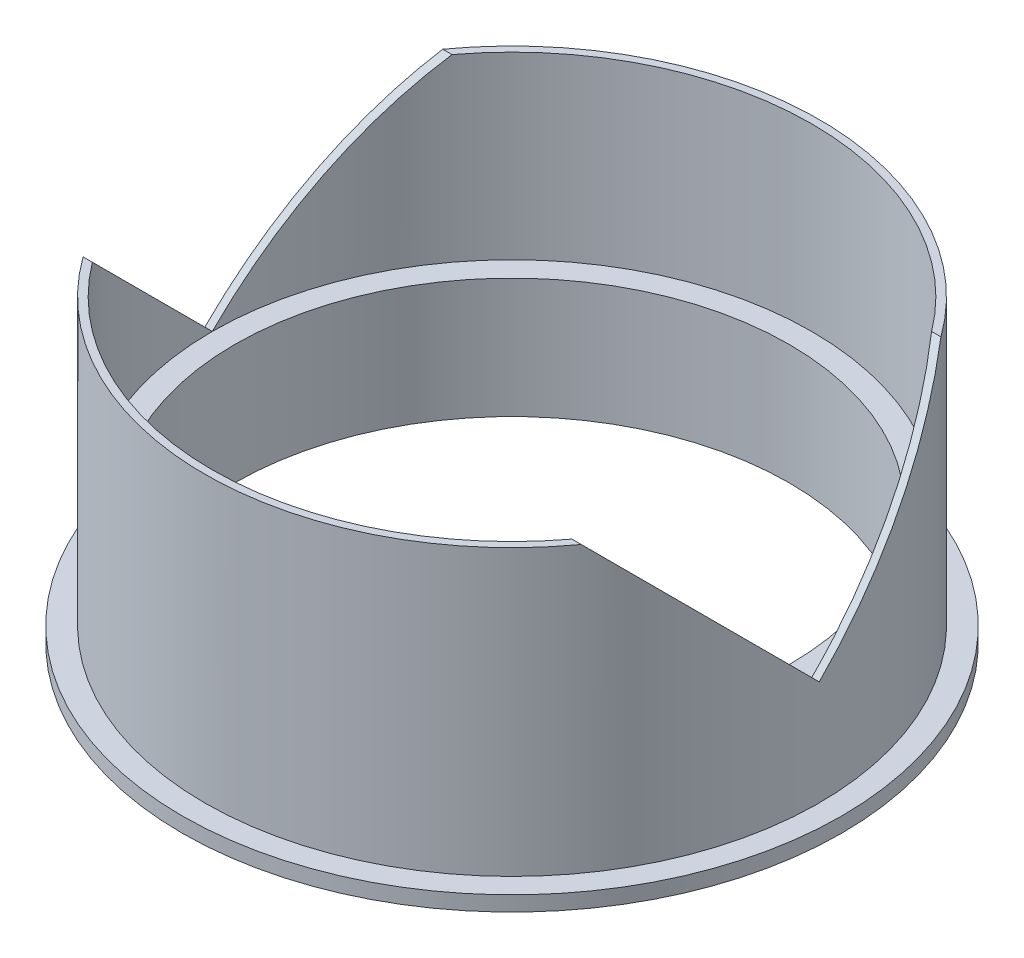
SolidWorks part; units mm, degrees
ref_plane "Front Plane" through (0, 0, 0) normal (0, 0, 1) x (1, 0, 0)
ref_plane "Top Plane" through (0, 0, 0) normal (0, 1, 0) x (1, 0, 0)
ref_plane "Right Plane" through (0, 0, 0) normal (1, 0, 0) x (0, 0, -1)
sketch "Sketch1" plane through (0, 0, 0) normal (0, 1, 0) x (1, 0, 0)
  circle A0 centre (0, 0) radius 130.175
  circle A1 centre (0, 0) radius 127
  circle A2 centre (0, 0) radius 139.7
  circle A3 centre (0, 0) radius 117.475
  dimension "D1" = 279.4
  dimension "D2" = 260.35
  dimension "D3" = 254
  dimension "D4" = 234.95
extrude "Boss-Extrude1" add sketch "Sketch1" along normal blind 50.8 contours A1 A3 region at (-123.4079, 0, 0)
extrude "Boss-Extrude2" add sketch "Sketch1<3>" along normal blind 254 contours A0 A1 region at (-129.8068, 0, 0)
sketch "Sketch1<3>" plane through (0, 0, 0) normal (0, 1, 0) x (1, 0, 0) same geometry as "Sketch1"
extrude "Boss-Extrude3" add sketch "Sketch1<4>" along normal blind 6.35 contours A2 A0 region at (-135.7487, 0, 0)
sketch "Sketch1<4>" plane through (0, 0, 0) normal (0, 1, 0) x (1, 0, 0) same geometry as "Sketch1"
sketch "Sketch2" plane through (0, 0, 0) normal (1, 0, 0) x (0, 0, -1)
  line L0 (-130.175, 254) -> (-130.175, 6.35) construction
  line L1 (-130.175, 127) -> (0, 127)
  line L2 (-130.175, 127) -> (-130.175, 254)
  line L3 (-130.175, 254) -> (0, 254)
  line L5 (117.475, 50.8) -> (-117.475, 50.8) construction
  line L6 (0, 254) -> (0, 127) construction
  line L7 (0, 254) -> (0, 127)
  line L8 (130.175, 254) -> (-130.175, 254) construction
  dimension "D1" = 76.2
revolve "Cut-Revolve4" cut sketch "Sketch2" angle 360 about L6
sketch "Sketch3" plane through (0, 0, 0) normal (1, 0, 0) x (0, 0, -1)
  line L0 (-76.2, 127) -> (76.2, 127)
  line L1 (130.175, 127) -> (-130.175, 127) construction
  line L2 (76.2, 127) -> (0, 50.8)
  line L4 (0, 50.8) -> (-76.2, 127)
  line L5 (127, 127) -> (-127, 127) construction
  line L6 (0, 127) -> (0, 50.8) construction
  line L8 (117.475, 50.8) -> (-117.475, 50.8) construction
  point P4 (0, 127)
  point P6 (0, 50.6123)
  point P11 (-8.8782, 87.2707)
  point P12 (-63.8658, 127)
  point P13 (27.4938, 86.6979)
  point P14 (-2.2911, 50.8)
  point P16 (0, 0)
  dimension "D1" = 45
extrude "Cut-Extrude1" cut sketch "Sketch3" against normal through all both and the other way through all
equation "\"Tube_ID\"= 10in"
equation "\"Tube_OD\" = 10.25in"
equation "\"Tube_Chute_ID\"= 9.25in"
equation "\"Tube_Flange_OD\"= 11in"
equation "\"Flange_Thickness\"= 0.25in"
equation "\"Chute_Height\"= 2in"
equation "\"Tube_Height\"= 10in"
equation "\"D4@Sketch1\"=\"Tube_Chute_ID\""
equation "\"D2@Sketch1\"=\"Tube_OD\""
equation "\"D1@Sketch1\"=\"Tube_Flange_OD\""
equation "\"D3@Sketch1\"=\"Tube_ID\""
